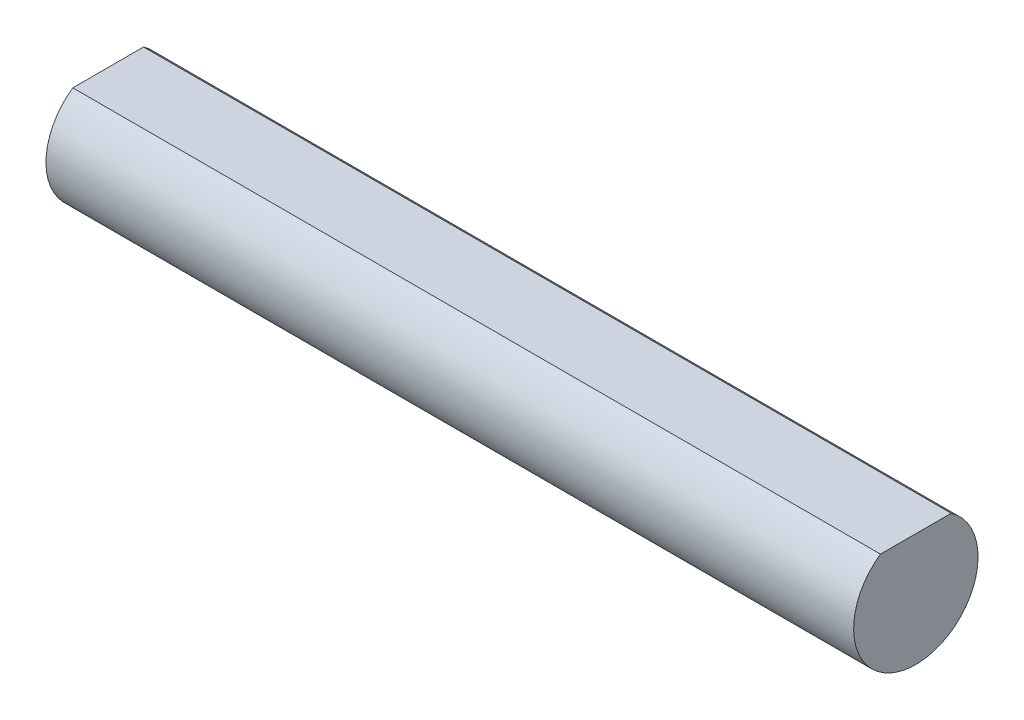
SolidWorks part; units mm, degrees
ref_plane "Front Plane" through (0, 0, 0) normal (0, 0, 1) x (1, 0, 0)
ref_plane "Top Plane" through (0, 0, 0) normal (0, 1, 0) x (1, 0, 0)
ref_plane "Right Plane" through (0, 0, 0) normal (1, 0, 0) x (0, 0, -1)
sketch "Sketch1" plane through (0, 0, 0) normal (1, 0, 0) x (0, 0, -1)
  line L1 (1.0951, 1.5832) -> (-1.0951, 1.5832)
  arc A0 (-1.0951, 1.5832) -> (1.0951, 1.5832) centre (0, 0) ccw
  dimension "D1" = 3.85
extrude "Boss-Extrude1" add sketch "Sketch1" along normal mid plane 25
